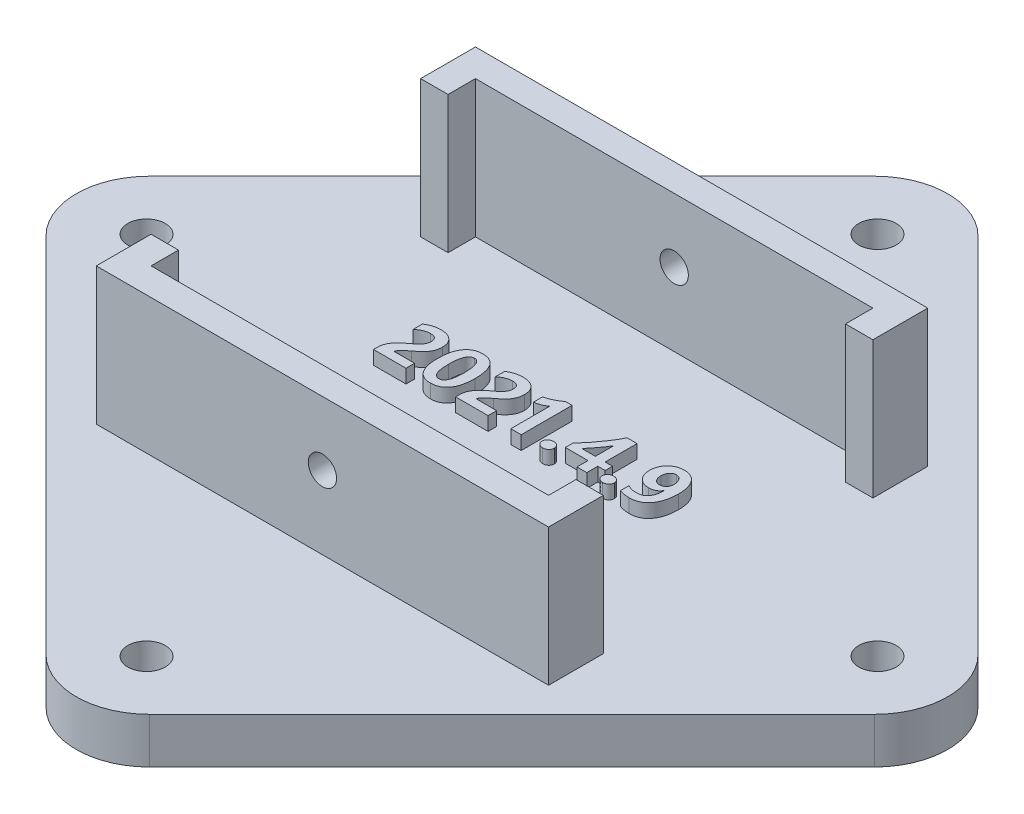
SolidWorks part; units mm, degrees
ref_plane "前视基准面" through (0, 0, 0) normal (0, 0, 1) x (1, 0, 0)
ref_plane "上视基准面" through (0, 0, 0) normal (0, 1, 0) x (1, 0, 0)
ref_plane "右视基准面" through (0, 0, 0) normal (1, 0, 0) x (0, 0, -1)
sketch "草图1" plane through (0, 0, 0) normal (0, 1, 0) x (1, 0, 0)
  line L1 (-5.6569, 45.3431) -> (-45.3431, 5.6569)
  line L2 (-45.3431, -5.6569) -> (-5.6569, -45.3431)
  line L3 (5.6569, -45.3431) -> (45.3431, -5.6569)
  line L4 (45.3431, 5.6569) -> (5.6569, 45.3431)
  circle A0 centre (0, 0) radius 36.0624 construction
  circle A1 centre (0, 40) radius 2.05
  circle A2 centre (40, 0) radius 2.05
  circle A3 centre (0, -40) radius 2.05
  circle A4 centre (-40, 0) radius 2.05
  arc A5 (-45.3431, 5.6569) -> (-45.3431, -5.6569) centre (-39.6863, 0) ccw
  arc A6 (-5.6569, -45.3431) -> (5.6569, -45.3431) centre (0, -39.6863) ccw
  arc A7 (45.3431, 5.6569) -> (45.3431, -5.6569) centre (39.6863, 0) cw
  arc A8 (5.6569, 45.3431) -> (-5.6569, 45.3431) centre (0, 39.6863) ccw
  point P18 (0, 0)
  point P25 (0, 51)
  dimension "D3" = 4.1
  dimension "D5" = 8
  dimension "D1" = 51
  dimension "D4" = 40
  dimension "D2" = 4
extrude "凸台-拉伸1" add sketch "草图1" along normal blind 5
sketch "草图2" plane through (0, 5, 0) normal (0, 1, 0) x (1, 0, 0)
  line L0 (-24.75, 14.75) -> (-21.75, 14.75)
  line L1 (24.75, -20.75) -> (-24.75, -20.75)
  line L2 (24.75, -20.75) -> (24.75, -14.75)
  line L3 (24.75, 20.75) -> (-24.75, 20.75)
  line L4 (-24.75, -20.75) -> (-24.75, -14.75)
  line L5 (24.75, -20.75) -> (-24.75, 20.75) construction
  line L6 (24.75, 20.75) -> (-24.75, -20.75) construction
  line L7 (21.75, -17.75) -> (-21.75, -17.75)
  line L8 (21.75, -17.75) -> (21.75, -14.75)
  line L9 (21.75, 17.75) -> (-21.75, 17.75)
  line L10 (-21.75, -17.75) -> (-21.75, -14.75)
  line L11 (21.75, -17.75) -> (-21.75, 17.75) construction
  line L12 (21.75, 17.75) -> (-21.75, -17.75) construction
  line L13 (0, 0) -> (-10.7692, 0) construction
  line L14 (0, 0) -> (0, 9.6792) construction
  line L15 (-24.75, -14.75) -> (-21.75, -14.75)
  line L16 (24.75, -14.75) -> (21.75, -14.75)
  line L17 (24.75, 14.75) -> (21.75, 14.75)
  line L18 (-21.75, 14.75) -> (-21.75, 17.75)
  line L19 (-24.75, 14.75) -> (-24.75, 20.75)
  line L20 (24.75, 14.75) -> (24.75, 20.75)
  line L21 (21.75, 14.75) -> (21.75, 17.75)
  point P0 (0, 0)
  point P6 (0, 0)
  dimension "D1" = 49.5
  dimension "D2" = 41.5
  dimension "D3" = 3
  dimension "D4" = 3
  dimension "D5" = 6
extrude "凸台-拉伸2" add sketch "草图2" along normal blind 15
sketch "草图3" plane through (0, 0, 20.75) normal (0, 0, 1) x (1, 0, 0)
  line L0 (-24.75, 5) -> (24.75, 5) construction
  line L1 (-5.6569, 0) -> (5.6569, 0) construction
  circle A0 centre (0, 13) radius 1.55
  point P5 (0, 0)
  dimension "D1" = 3.1
  dimension "D2" = 8
extrude "切除-拉伸1" cut sketch "草图3" against normal through all and the other way through all
sketch "草图4" plane through (0, 5, 0) normal (0, 1, 0) x (1, 0, 0)
  line L0 (-19.0222, 0) -> (19.0222, 0) construction
  text T0 "2021.4.9" font "微软雅黑" height 5.5
  point P3 (0, 0)
  point P4 (0, 0)
  point P5 (0, 0)
  point P7 (-19.0222, 0)
extrude "凸台-拉伸3" add sketch "草图4" along normal blind 1.5
